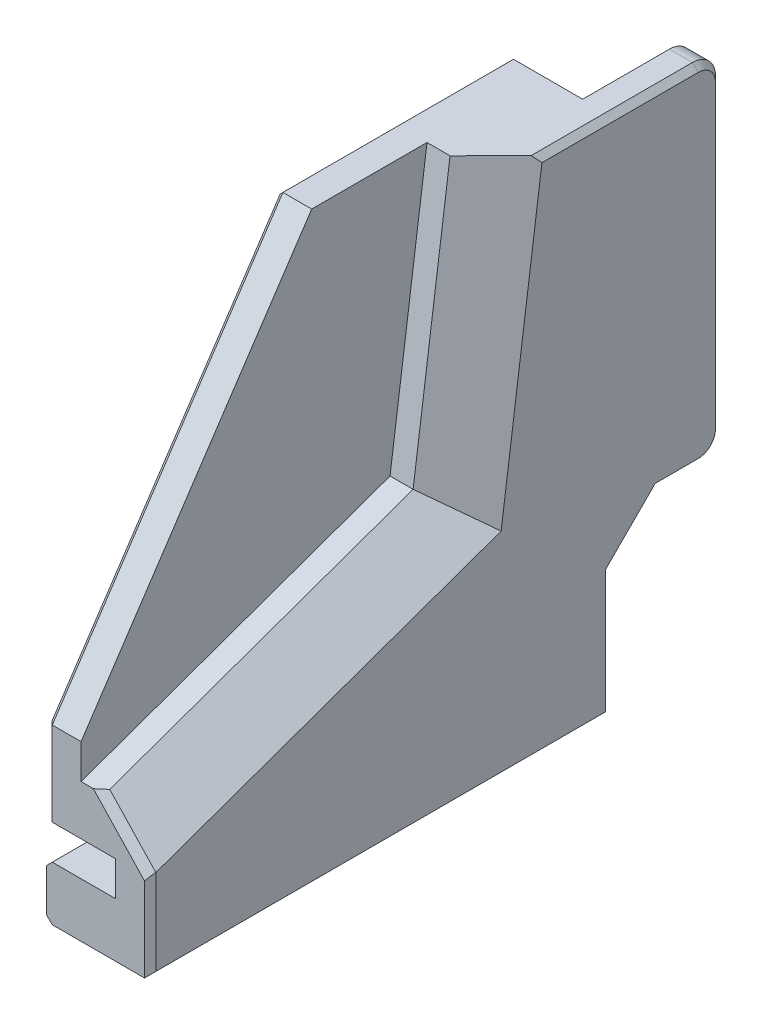
SolidWorks part; units mm, degrees
note: The reader was unsure of these and kept them because the rebuilt part matched: shared geometry of "Sketch1<3>".
ref_plane "Front Plane" through (0, 0, 0) normal (0, 0, 1) x (1, 0, 0)
ref_plane "Top Plane" through (0, 0, 0) normal (0, 1, 0) x (1, 0, 0)
ref_plane "Right Plane" through (0, 0, 0) normal (1, 0, 0) x (0, 0, -1)
sketch "Sketch1" plane through (0, 0, 0) normal (0, 0, 1) x (1, 0, 0)
  line L1 (0, 0) -> (9, 0)
  line L2 (0, 0) -> (0, 45)
  line L3 (0, 45) -> (9, 45)
  line L4 (9, 0) -> (9, 45)
  circle A0 centre (6, 25) radius 1.6319
  circle A1 centre (6, 13) radius 1.6319
  dimension "D3" = 3.2639
  dimension "D1" = 9
  dimension "D2" = 45
  dimension "D4" = 3
  dimension "D5" = 12
  dimension "D6" = 20
extrude "Boss-Extrude1" add sketch "Sketch1" along normal blind 40 contours L1 L4 L3 L2 A1 A0 | A0 | A1
extrude "Cut-Extrude1" cut sketch "Sketch1<3>" along normal blind 10 contours A0 | A1
sketch "Sketch1<3>" plane through (0, 0, 0) normal (0, 0, 1) x (1, 0, 0) same geometry as "Sketch1"
sketch "Sketch2" plane through (9, 0, 0) normal (1, 0, 0) x (0, 0, -1)
  line L0 (0, 0) -> (0, 45) construction
  line L1 (0, 4.7) -> (-40, 4.7)
  line L2 (0, 4.7) -> (0, 7.7)
  line L3 (0, 7.7) -> (-40, 7.7)
  line L4 (-40, 4.7) -> (-40, 7.7)
  line L5 (-40, 0) -> (-40, 45) construction
  line L6 (-40, 0) -> (0, 0) construction
  dimension "D1" = 3
  dimension "D2" = 7.7
extrude "Cut-Extrude2" cut sketch "Sketch2" against normal blind 6
sketch "Sketch3" plane through (9, 0, 0) normal (1, 0, 0) x (0, 0, -1)
  line L0 (-20, 45) -> (-40, 15)
  line L1 (-40, 45) -> (0, 45) construction
  line L2 (-40, 7.7) -> (-40, 45) construction
  line L3 (-40, 0) -> (0, 0) construction
  line L4 (0, 0) -> (0, 45) construction
  line L5 (-40, 15) -> (-48.3794, 51.9132)
  line L6 (-48.3794, 51.9132) -> (-20, 45)
  dimension "D1" = 15
  dimension "D2" = 20
extrude "Cut-Extrude3" cut sketch "Sketch3" against normal up to surface (9 mm away) up to face at (0, 22.5, 20)
sketch "Sketch4" plane through (0, 0, 0) normal (-1, 0, 0) x (0, 0, 1)
  line L0 (15, 45) -> (15, 15)
  line L1 (20, 45) -> (0, 45) construction
  line L2 (15, 15) -> (-9.525, 15)
  line L3 (-9.525, 15) -> (-9.525, 45)
  line L4 (-9.525, 45) -> (15, 45)
  line L6 (0, 0) -> (0, 45) construction
  line L7 (0, 0) -> (0, 45) construction
  dimension "D1" = 30
  dimension "D2" = 15
  dimension "D3" = 9.525
sketch "Sketch5" plane through (0, 0, 0) normal (-1, 0, 0) x (0, 0, 1)
  line L0 (10, 45) -> (13.2048, 21.5521)
  line L1 (13.2048, 21.5521) -> (40, 12)
  line L5 (40, 15) -> (20, 45)
  line L6 (20, 45) -> (0, 45)
  line L7 (0, 45) -> (0, 0)
  line L8 (0, 0) -> (40, 0)
  line L9 (40, 0) -> (40, 15)
  line L10 (40, 15) -> (20, 45)
  line L11 (20, 45) -> (0, 45)
  line L12 (0, 45) -> (0, 0)
  line L13 (0, 0) -> (40, 0)
  line L14 (40, 0) -> (40, 15)
  line M6 (40, 15) -> (20, 45)
  line M7 (20, 45) -> (0, 45)
  line M10 (40, 0) -> (40, 15)
  dimension "D2" = 10
  dimension "D3" = 12
  dimension "D1" = 0
extrude "Cut-Extrude4" cut sketch "Sketch5" against normal blind 6 contours L0 L1 M10 M6 M7
chamfer "Chamfer2" distance 4 angle 45 2 edges at (0, 16.7761, 26.6024) (0, 33.2761, 11.6024)
sketch "Sketch6" plane through (0, 0, 0) normal (0, -1, 0) x (1, 0, 0)
  line L0 (0, 40) -> (9, 40) construction
  line L1 (9, 40) -> (9, 0) construction
  circle A0 centre (5.5, 35) radius 2.0193
  circle A1 centre (5.5, 20) radius 2.0193
  dimension "D1" = 4.0386
  dimension "D4" = 3.5
  dimension "D2" = 15
  dimension "D3" = 5
extrude "Cut-Extrude5" cut sketch "Sketch6" against normal blind 6
sketch "Sketch7" plane through (0, 0, 0) normal (0, 0, -1) x (-1, 0, 0)
  line L1 (0, 45) -> (-3, 45)
  line L2 (0, 45) -> (0, 15)
  line L3 (0, 15) -> (-3, 15)
  line L4 (-3, 45) -> (-3, 15)
  dimension "D1" = 3
  dimension "D2" = 30
extrude "Boss-Extrude3" add sketch "Sketch7" along normal blind 9.52
chamfer "Chamfer3" distance 4 angle 45 1 edges at (1.5, 15, 0)
fillet "Fillet1" radius 2 2 edges at (1.5, 15, -9.52) (1.5, 45, -9.52)
chamfer "Chamfer4" distance 0.5 angle 45 23 edges at (3, 45, -3.76) (3, 44.4142, -8.9342) (3, 15, -5.76) (3, 30, -9.52) (3, 15.5858, -8.9342) (3, 13, -2) (9, 7.7, 20) (9, 4.7, 20) (0, 3.8767, 40) (0, 0, 20) (0, 5.5, 0) (0, 13, -2) (0, 15, -5.76) (0, 45, -0.7786) (0, 15.5858, -8.9342) (0, 44.4142, -8.9342) (0, 30, -9.52) (2, 9.8767, 40) (9, 0, 20) (9, 11.35, 40) (9, 30, 30) (9, 45, 10) (9, 26.35, 0)
mirror "Mirror1" about plane through (9, 0, 40) normal (-1, 0, 0) of bodies 108
sketch "Sketch8" plane through (0, 0, 0) normal (-1, 0, 0) x (0, 0, 1)
  line L1 (-21.4971, 55.9325) -> (52.2685, 55.9325)
  line L2 (-21.4971, 55.9325) -> (-21.4971, -6.8367)
  line L3 (-21.4971, -6.8367) -> (52.2685, -6.8367)
  line L4 (52.2685, 55.9325) -> (52.2685, -6.8367)
extrude "Cut-Extrude6" cut sketch "Sketch8" against normal blind 9
